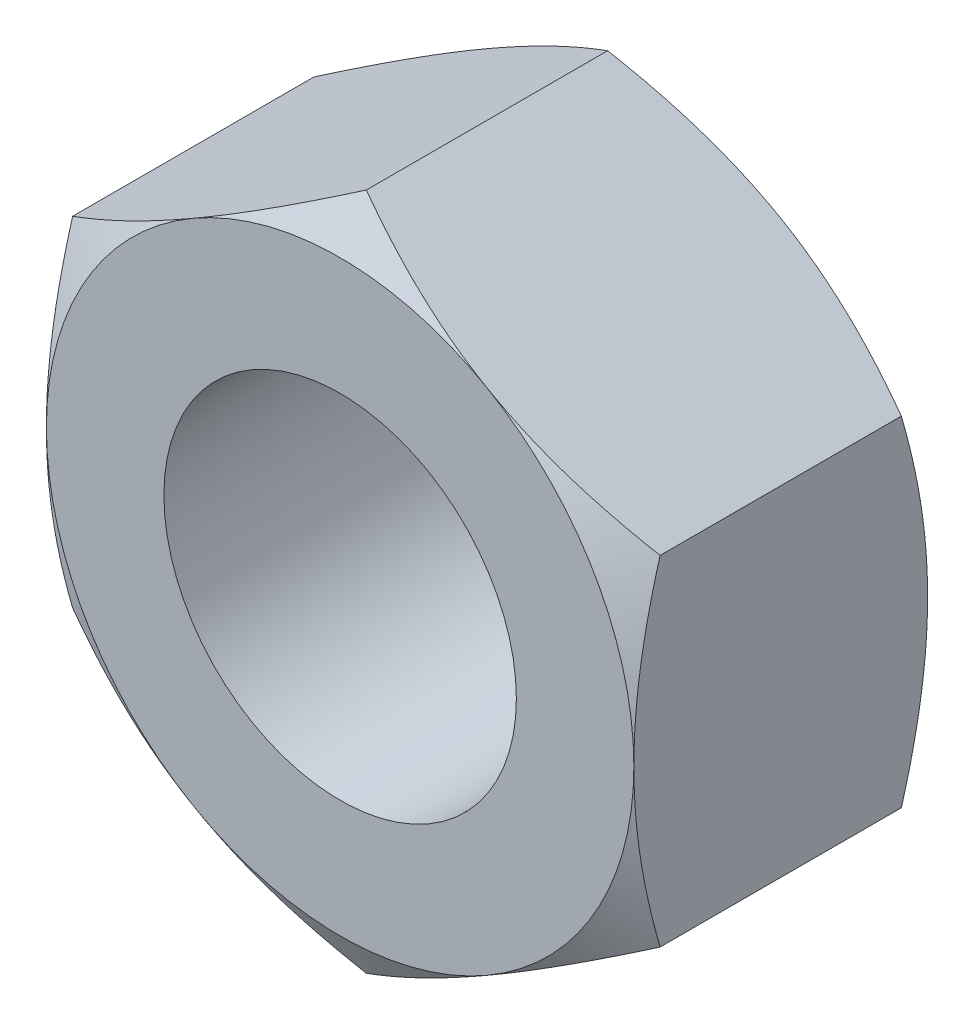
SolidWorks part; units mm, degrees
ref_plane "Plan1" through (0, 0, 0) normal (0, 0, 1) x (1, 0, 0)
ref_plane "Plan2" through (0, 0, 0) normal (0, 1, 0) x (1, 0, 0)
ref_plane "Plan3" through (0, 0, 0) normal (1, 0, 0) x (0, 0, -1)
sketch "Esquisse1" plane through (0, 0, 0) normal (0, 0, 1) x (1, 0, 0)
  line L0 (0, 0) -> (5, 0) construction
  line L1 (5, -2.8868) -> (5, 2.8868)
  line L2 (0, 0) -> (5, 2.8868) construction
  line L3 (0, 0) -> (0, 5.7735) construction
  line L4 (5, 2.8868) -> (0, 5.7735)
  line L5 (5, -2.8868) -> (0, -5.7735)
  line L6 (-5, -2.8868) -> (0, -5.7735)
  line L7 (-5, -2.8868) -> (-5, 2.8868)
  line L8 (-5, 2.8868) -> (0, 5.7735)
  circle A0 centre (0, 0) radius 5 construction
  circle A1 centre (0, 0) radius 5.7735 construction
  dimension "D2" = 10
  dimension "D1" = 30
extrude "Base-Extrusion" add sketch "Esquisse1" against normal blind 5
sketch "Esquisse2" plane through (0, 0, 0) normal (0, 1, 0) x (1, 0, 0)
  line L0 (-5, 0) -> (-10.3301, 0)
  line L1 (0, 5) -> (0, 0) construction
  line L2 (-5, 5) -> (-10.3301, 5)
  line L3 (-10.3301, 5) -> (-10.3301, 0)
  line L5 (-9.3301, 2.5) -> (-5, 5)
  line L6 (0, 5) -> (0, 0) construction
  line L7 (-5, 0) -> (-9.3301, 2.5)
  dimension "D1" = 30
  dimension "D2" = 1
  dimension "D3" = 30
revolve "Enlèvement de matière-Révolution1" cut sketch "Esquisse2" angle 360 about L6
sketch "Esquisse3" plane through (0, 0, 0) normal (0, 0, 1) x (1, 0, 0)
  circle A0 centre (0, 0) radius 3
  dimension "D1" = 6
extrude "Enlèv. mat.-Extru.1" cut sketch "Esquisse3" against normal through all
ref_axis "Axe1" through (0, 0, -50) along (0, 0, 1)
